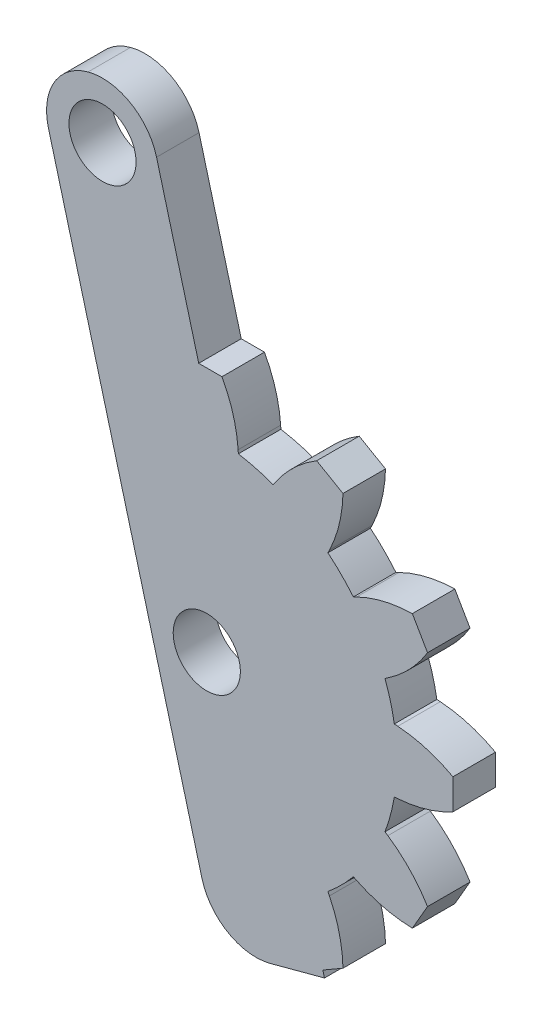
SolidWorks part; units mm, degrees
ref_plane "Front Plane" through (0, 0, 0) normal (0, 0, 1) x (1, 0, 0)
ref_plane "Top Plane" through (0, 0, 0) normal (0, 1, 0) x (1, 0, 0)
ref_plane "Right Plane" through (0, 0, 0) normal (1, 0, 0) x (0, 0, -1)
sketch "Sketch1" plane through (0, 0, 0) normal (0, 0, 1) x (1, 0, 0)
  circle A0 centre (0, 0) radius 8.5
  dimension "D1" = 17
extrude "Boss-Extrude1" add sketch "Sketch1" along normal blind 1.9
sketch "Sketch2" plane through (0, 0, 1.9) normal (0, 0, 1) x (1, 0, 0)
  line L0 (0, 0) -> (0, 12.8785) construction
  line L1 (0, 0) -> (1.4399, 10.9374) construction
  line L2 (0, 0) -> (-1.4446, 10.9725) construction
  line L3 (0, 0) -> (-3.4108, 12.7294) construction
  circle A0 centre (0, 0) radius 10 construction
  circle A1 centre (0, 0) radius 2.5 construction
  dimension "D3" = 20
  dimension "D5" = 5
  dimension "D1" = 7.5
  dimension "D2" = 7.5
  dimension "D4" = 15
ref_point "Point3"
ref_point "Point4"
sketch "Sketch3" plane through (0, 0, 1.9) normal (0, 0, 1) x (1, 0, 0)
  line L0 (-1.3053, 9.9144) -> (-1.5091, 7)
  line L1 (-1.5091, 7) -> (1.5091, 7)
  line L2 (1.3053, 9.9144) -> (1.5091, 7)
  line L3 (1.3053, 9.9144) -> (0.6785, 11)
  line L4 (-1.3053, 9.9144) -> (-0.6785, 11)
  line L5 (-0.6785, 11) -> (0.6785, 11)
  dimension "D1" = 11
  dimension "D2" = 7
  dimension "D3" = 60
  dimension "D4" = 86
  dimension "D5" = 60
  dimension "D6" = 86
extrude "Boss-Extrude2" add sketch "Sketch3" against normal blind 1.9
pattern_circular "CirPattern2" count 12 over 360 about axis through (0, 0, 1.9) along (0, 0, -1) of "Boss-Extrude2"
fillet "Fillet5" radius 6 12 edges at (9.2388, 3.8268, 0.95) (6.0876, 7.9335, 0.95) (1.3053, 9.9144, 0.95) (-3.8268, 9.2388, 0.95) (-7.9335, 6.0876, 0.95) (-9.9144, 1.3053, 0.95) (-9.2388, -3.8268, 0.95) (-6.0876, -7.9335, 0.95) (-1.3053, -9.9144, 0.95) (3.8268, -9.2388, 0.95) (7.9335, -6.0876, 0.95) (9.9144, -1.3053, 0.95)
fillet "Fillet6" radius 6 12 edges at (7.9335, 6.0876, 0.95) (3.8268, 9.2388, 0.95) (-1.3053, 9.9144, 0.95) (-6.0876, 7.9335, 0.95) (-9.2388, 3.8268, 0.95) (-9.9144, -1.3053, 0.95) (-7.9335, -6.0876, 0.95) (-3.8268, -9.2388, 0.95) (1.3053, -9.9144, 0.95) (6.0876, -7.9335, 0.95) (9.2388, -3.8268, 0.95) (9.9144, 1.3053, 0.95)
sketch "Sketch12" plane through (0, 0, 0) normal (0, 0, -1) x (-1, 0, 0)
  line L0 (0, 0) -> (0, 13.7449) construction
  line L1 (0, 0) -> (3.8761, 14.4659) construction
  line L2 (1.5359, 15.3913) -> (-5.2618, -9.9781)
  line L3 (-5.2618, -9.9781) -> (-0.4322, -11.2722)
  line L4 (-0.4322, -11.2722) -> (7.7206, 19.1544)
  line L5 (1.5359, 15.3913) -> (2.891, 20.4485)
  line L6 (2.891, 20.4485) -> (7.7206, 19.1544)
  circle A0 centre (0, 0) radius 2.5 construction
  dimension "D2" = 5
  dimension "D1" = 15
  dimension "D3" = 15
  dimension "D4" = 90
  dimension "D5" = 90
  dimension "D6" = 2.5
  dimension "D7" = 5
  dimension "D8" = 2.5
  dimension "D9" = 11
  dimension "D10" = 20.5
extrude "Boss-Extrude5" add sketch "Sketch12" against normal blind 1.9
sketch "Sketch14" plane through (0, 0, 0) normal (0, 0, -1) x (-1, 0, 0)
  circle A0 centre (0, 0) radius 1.5
  dimension "D1" = 3
sketch "Sketch15" plane through (0, 0, 0) normal (0, 0, -1) x (-1, 0, 0)
  circle A0 centre (0, 0) radius 5
  dimension "D1" = 10
extrude "Boss-Extrude6" add sketch "Sketch15" against normal blind 1.9
extrude "Cut-Extrude7" cut sketch "Sketch14" against normal through all
sketch "Sketch16" plane through (0, 0, 1.9) normal (0, 0, 1) x (1, 0, 0)
  line L0 (-5.659, 11.4605) -> (0.4322, -11.2722)
  line L1 (-5.1889, 9.7059) -> (-7.7206, 19.1544) construction
  line L2 (0.4322, -11.2722) -> (-8.6915, -13.7169)
  line L3 (-8.6915, -13.7169) -> (-14.7827, 9.0158)
  line L4 (-14.7827, 9.0158) -> (-5.659, 11.4605)
extrude "Cut-Extrude8" cut sketch "Sketch16" against normal through all
sketch "Sketch17" plane through (0, 0, 1.9) normal (0, 0, 1) x (1, 0, 0)
  circle A0 centre (-4.6587, 17.3867) radius 1.5
  circle A1 centre (0, 0) radius 1.5 construction
  dimension "D1" = 3
  dimension "D2" = 18
extrude "Cut-Extrude9" cut sketch "Sketch17" against normal through all
ref_axis "Axis1" through (0, 0, 1.9) along (0, 0, -1)
sketch "Sketch18" plane through (0, 0, 0) normal (0, 0, 1) x (1, 0, 0)
  line L0 (0, 0) -> (8.2104, 2.2) construction
  arc A0 (8.3818, 1.4124) -> (7.9651, 2.9677) centre (0, 0) ccw construction
fillet "Fillet7" radius 2.5 3 edges at (-7.7206, 19.1544, 0.95) (-2.891, 20.4485, 0.95) (0.4322, -11.2722, 0.95)
